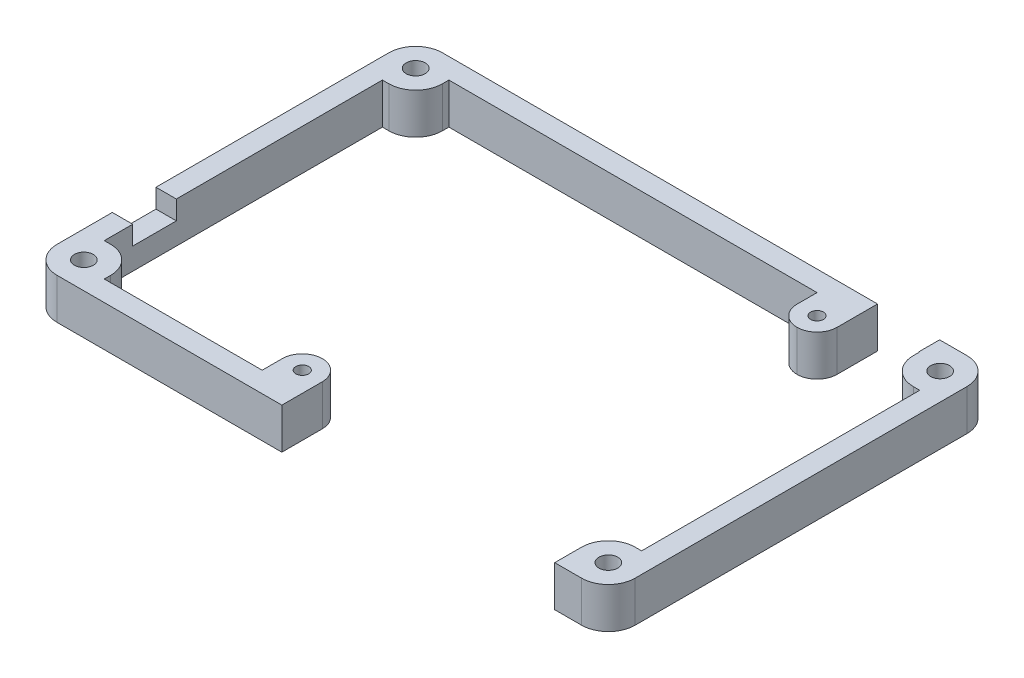
SolidWorks part; units mm, degrees
material "Rubber"
ref_plane "Front" through (0, 0, 0) normal (0, 0, 1) x (1, 0, 0)
ref_plane "Top" through (0, 0, 0) normal (0, 1, 0) x (1, 0, 0)
ref_plane "Right" through (0, 0, 0) normal (1, 0, 0) x (0, 0, -1)
sketch "Sketch1" plane through (0, 0, 0) normal (0, 1, 0) x (1, 0, 0)
  line L0 (-45, 0) -> (45, 0) construction
  line L1 (-45, 30) -> (45, 30) construction
  line L2 (-45, 30) -> (-45, -30) construction
  line L3 (-45, -30) -> (45, -30) construction
  line L4 (45, 30) -> (45, -30) construction
  line L5 (0, -30) -> (0, 30) construction
  line L6 (41.825, 26.825) -> (41.825, -26.825) construction
  line L7 (-41.825, -26.825) -> (41.825, -26.825) construction
  line L8 (-41.825, 26.825) -> (-41.825, -26.825) construction
  line L9 (-41.825, 26.825) -> (41.825, 26.825) construction
  line L10 (40.825, 25.825) -> (40.825, -25.825) construction
  line L11 (-40.825, -25.825) -> (40.825, -25.825) construction
  line L12 (-40.825, 25.825) -> (-40.825, -25.825) construction
  line L13 (-40.825, 25.825) -> (40.825, 25.825) construction
  line L14 (40.825, 21.65) -> (45, 21.65) construction
  line L15 (40.825, -21.65) -> (45, -21.65) construction
  line L16 (36.65, -25.825) -> (36.65, -30) construction
  line L17 (-36.65, -25.825) -> (-36.65, -30) construction
  line L18 (-40.825, -21.65) -> (-45, -21.65) construction
  line L19 (-36.65, 25.825) -> (-36.65, 30) construction
  line L20 (-40.825, 21.65) -> (-45, 21.65) construction
  line L21 (36.65, 25.825) -> (36.65, 30) construction
  line L22 (40.825, -25.825) -> (41.825, -25.825) construction
  circle A0 centre (-40.825, -25.825) radius 1 construction
  circle A1 centre (40.825, -25.825) radius 1 construction
  circle A2 centre (40.825, 25.825) radius 1 construction
  circle A3 centre (-40.825, 25.825) radius 1 construction
  circle A4 centre (40.825, -25.825) radius 4.175 construction
  circle A5 centre (40.825, 25.825) radius 4.175 construction
  circle A6 centre (-40.825, 25.825) radius 4.175 construction
  circle A7 centre (-40.825, -25.825) radius 4.175 construction
  dimension "D1" = 90
  dimension "D2" = 60
  dimension "D4" = 1
  dimension "D3" = 3.175
sketch "Sketch2" plane through (0, 0, 0) normal (0, 1, 0) x (1, 0, 0)
  line L0 (-45, 30) -> (-45, -30) construction
  line L1 (-45, -30) -> (45, -30) construction
  line L2 (45, 30) -> (45, -30) construction
  line L3 (-45, 30) -> (45, 30) construction
  line L4 (40.825, 21.65) -> (45, 21.65) construction
  line L5 (36.65, 25.825) -> (36.65, 30) construction
  line L6 (-36.65, 25.825) -> (-36.65, 30) construction
  line L7 (-40.825, 21.65) -> (-45, 21.65) construction
  line L8 (-36.65, -25.825) -> (-36.65, -30) construction
  line L9 (-40.825, -21.65) -> (-45, -21.65) construction
  line L10 (36.65, -25.825) -> (36.65, -30) construction
  line L11 (40.825, -21.65) -> (45, -21.65) construction
  line L16 (-45, 25.825) -> (-45, -25.825)
  line L17 (-40.825, -30) -> (40.825, -30)
  line L18 (45, 25.825) -> (45, -25.825)
  line L19 (-40.825, 30) -> (40.825, 30)
  line L20 (40.825, 21.65) -> (41.825, 21.65)
  line L21 (36.65, 25.825) -> (36.65, 26.825)
  line L22 (-36.65, 25.825) -> (-36.65, 26.825)
  line L23 (-40.825, 21.65) -> (-41.825, 21.65)
  line L24 (-36.65, -25.825) -> (-36.65, -26.825)
  line L25 (-40.825, -21.65) -> (-41.825, -21.65)
  line L26 (36.65, -25.825) -> (36.65, -26.825)
  line L27 (40.825, -21.65) -> (41.825, -21.65)
  line L28 (41.825, 26.825) -> (41.825, -26.825) construction
  line L29 (-36.65, -26.825) -> (36.65, -26.825)
  line L30 (-41.825, 26.825) -> (41.825, 26.825) construction
  line L31 (-41.825, 26.825) -> (-41.825, -26.825) construction
  line L32 (-36.65, 26.825) -> (36.65, 26.825)
  line L33 (-41.825, 21.65) -> (-41.825, -21.65)
  line L34 (41.825, 21.65) -> (41.825, -21.65)
  line L35 (-41.825, -26.825) -> (41.825, -26.825) construction
  circle A0 centre (40.825, 25.825) radius 4.175 construction
  circle A1 centre (40.825, 25.825) radius 1 construction
  circle A2 centre (-40.825, 25.825) radius 4.175 construction
  circle A3 centre (-40.825, 25.825) radius 1 construction
  circle A4 centre (-40.825, -25.825) radius 4.175 construction
  circle A5 centre (40.825, -25.825) radius 4.175 construction
  arc A6 (45, 25.825) -> (40.825, 30) centre (40.825, 25.825) ccw
  circle A7 centre (40.825, 25.825) radius 1 construction
  arc A8 (-40.825, 30) -> (-45, 25.825) centre (-40.825, 25.825) ccw
  circle A9 centre (-40.825, 25.825) radius 1 construction
  arc A10 (-36.65, -25.825) -> (-40.825, -21.65) centre (-40.825, -25.825) ccw
  arc A11 (40.825, -21.65) -> (36.65, -25.825) centre (40.825, -25.825) ccw
  circle A12 centre (-40.825, -25.825) radius 1 construction
  circle A13 centre (40.825, -25.825) radius 1 construction
  circle A14 centre (-40.825, -25.825) radius 1 construction
  circle A15 centre (40.825, -25.825) radius 1 construction
  arc A16 (-40.825, 21.65) -> (-36.65, 25.825) centre (-40.825, 25.825) ccw
  arc A17 (-45, -25.825) -> (-40.825, -30) centre (-40.825, -25.825) ccw
  arc A18 (40.825, -30) -> (45, -25.825) centre (40.825, -25.825) ccw
  arc A19 (36.65, 25.825) -> (40.825, 21.65) centre (40.825, 25.825) ccw
extrude "Boss-Extrude3" add sketch "Sketch2" along normal blind 6.35
sketch "Sketch3" plane through (0, 0, -30) normal (0, 0, -1) x (-1, 0, 0)
  line L0 (-40.825, 6.35) -> (40.825, 6.35) construction
  line L1 (-36.566, 6.35) -> (-26.9027, 6.35)
  line L2 (-36.566, 6.35) -> (-36.566, 0)
  line L3 (-36.566, 0) -> (-26.9027, 0)
  line L4 (-26.9027, 6.35) -> (-26.9027, 0)
  line L5 (-40.825, 0) -> (40.825, 0) construction
extrude "Cut-Extrude1" cut sketch "Sketch3" against normal up to vertex (3.175 mm away) up to point (36.65, 6.35, -26.825)
sketch "Sketch4" plane through (0, 0, 30) normal (0, 0, 1) x (1, 0, 0)
  line L0 (-40.825, 6.35) -> (40.825, 6.35) construction
  line L1 (36.65, 6.35) -> (-5.825, 6.35)
  line L2 (36.65, 6.35) -> (36.65, 0)
  line L3 (36.65, 0) -> (-5.825, 0)
  line L4 (-5.825, 6.35) -> (-5.825, 0)
  line L5 (-40.825, 0) -> (40.825, 0) construction
  line L6 (-40.825, 6.35) -> (-40.825, 0) construction
  dimension "D1" = 35
extrude "Cut-Extrude2" cut sketch "Sketch4" against normal up to vertex (3.175 mm away) up to point (36.65, 6.35, 26.825)
sketch "Sketch5" plane through (-45, 0, 0) normal (-1, 0, 0) x (0, 0, 1)
  line L0 (13.825, 6.35) -> (25.825, 6.35) construction
  line L1 (25.825, 6.35) -> (25.825, 0) construction
  line L3 (10.425, 9.3) -> (17.225, 9.3)
  line L4 (10.425, 9.3) -> (10.425, 3.4)
  line L5 (10.425, 3.4) -> (17.225, 3.4)
  line L6 (17.225, 9.3) -> (17.225, 3.4)
  line L7 (10.425, 9.3) -> (17.225, 3.4) construction
  line L8 (10.425, 3.4) -> (17.225, 9.3) construction
  dimension "D1" = 12
  dimension "D2" = 5.9
  dimension "D3" = 6.8
extrude "Cut-Extrude3" cut sketch "Sketch5" against normal up to surface (3.175 mm away) up to face at (-41.825, 3.175, 0)
sketch "Sketch7" plane through (0, 0, 0) normal (0, -1, 0) x (1, 0, 0)
  circle A0 centre (-40.825, -25.825) radius 1.4732
  circle A1 centre (-40.825, 25.825) radius 1.4732
  circle A2 centre (40.825, 25.825) radius 1.4732
  circle A3 centre (40.825, -25.825) radius 1.4732
  dimension "D1" = 2.9464
  dimension "D2" = 2.9464
  dimension "D3" = 2.9464
  dimension "D4" = 2.9464
extrude "Cut-Extrude4" cut sketch "Sketch7" against normal blind 10
sketch "Sketch10" plane through (0, 0, 26.825) normal (0, 0, -1) x (-1, 0, 0)
  line L0 (36.65, 0) -> (5.825, 0) construction
  line L1 (5.825, 6.35) -> (12.065, 6.35)
  line L2 (5.825, 6.35) -> (5.825, 0)
  line L3 (5.825, 0) -> (12.065, 0)
  line L4 (12.065, 6.35) -> (12.065, 0)
  dimension "D1" = 6.24
extrude "Boss-Extrude4" add sketch "Sketch10" along normal blind 6.24
sketch "Sketch11" plane through (0, 0, -26.825) normal (0, 0, 1) x (1, 0, 0)
  line L0 (26.9027, 6.35) -> (-36.65, 6.35) construction
  line L1 (26.9027, 0) -> (20.6627, 0)
  line L2 (26.9027, 0) -> (26.9027, 6.35)
  line L3 (26.9027, 6.35) -> (20.6627, 6.35)
  line L4 (20.6627, 0) -> (20.6627, 6.35)
  dimension "D1" = 6.24
extrude "Boss-Extrude5" add sketch "Sketch11" along normal blind 6.24
sketch "Sketch12" plane through (0, 6.35, 0) normal (0, 1, 0) x (1, 0, 0)
  line L0 (20.6627, 26.825) -> (26.9027, 20.585) construction
  circle A0 centre (23.7827, 23.705) radius 1
sketch "Sketch13" plane through (0, 6.35, 0) normal (0, 1, 0) x (1, 0, 0)
  line L0 (-12.065, -26.825) -> (-5.825, -20.585) construction
  circle A0 centre (-8.945, -23.705) radius 1
extrude "Cut-Extrude5" cut sketch "Sketch12" against normal through all
extrude "Cut-Extrude6" cut sketch "Sketch13" against normal through all
fillet "Fillet1" radius 3.12 4 edges at (26.9027, 3.175, -20.585) (20.6627, 3.175, -20.585) (-5.825, 3.175, 20.585) (-12.065, 3.175, 20.585)
